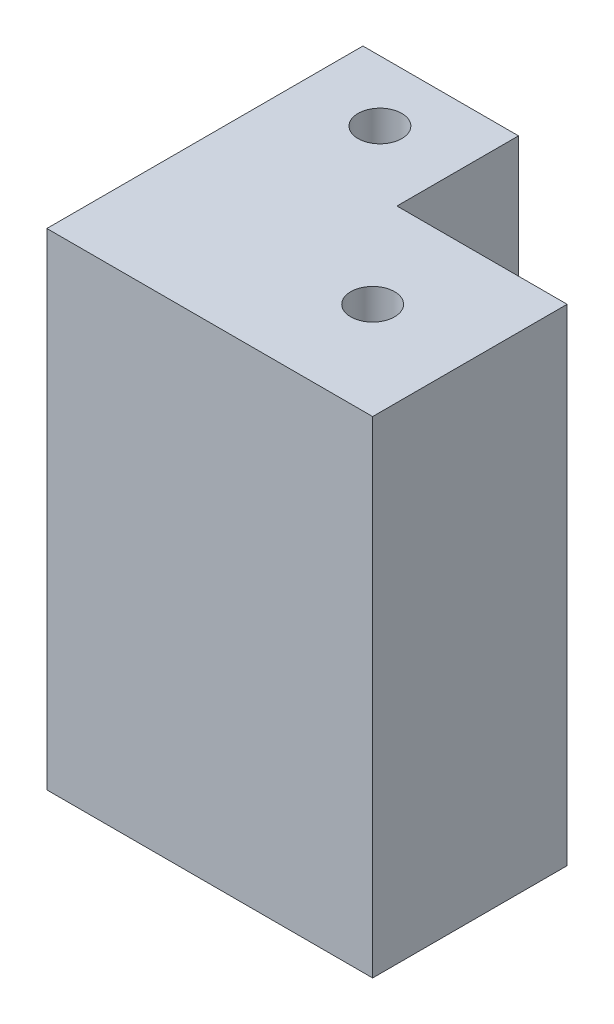
SolidWorks part; units mm, degrees
ref_plane "Front Plane" through (0, 0, 0) normal (0, 0, 1) x (1, 0, 0)
ref_plane "Top Plane" through (0, 0, 0) normal (0, 1, 0) x (1, 0, 0)
ref_plane "Right Plane" through (0, 0, 0) normal (1, 0, 0) x (0, 0, -1)
sketch "Sketch1" plane through (0, 0, 0) normal (0, 1, 0) x (1, 0, 0)
  line L0 (0, 0) -> (0, 25)
  line L1 (0, 25) -> (-32, 25)
  line L2 (-32, 25) -> (-32, -40)
  line L3 (-32, -40) -> (35, -40)
  line L4 (35, -40) -> (35, 0)
  line L5 (35, 0) -> (0, 0)
  line L6 (-32, 0) -> (0, 0) construction
  line L7 (0, -40) -> (0, 0) construction
  line L8 (0, 25) -> (-32, 0) construction
  line L9 (25, 25) -> (25, 0) construction
  line L10 (0, 25) -> (25, 25) construction
  line L11 (25, 0) -> (5, -40) construction
  line L12 (5, 5) -> (5, -40) construction
  line L13 (25, 25) -> (5, 25) construction
  line L14 (25, 25) -> (25, 5) construction
  line L15 (25, 5) -> (5, 5) construction
  line L16 (5, 25) -> (5, 5) construction
  circle A0 centre (-16, 12.5) radius 4.5
  circle A1 centre (15, -20) radius 4.5
  circle A2 centre (-16, 12.5) radius 11 construction
  circle A3 centre (-16, 12.5) radius 6 construction
  circle A4 centre (15, -20) radius 6.75 construction
  circle A5 centre (15, -20) radius 16 construction
  dimension "D4" = 9
  dimension "D5" = 22
  dimension "D6" = 12
  dimension "D7" = 13.5
  dimension "D8" = 32
  dimension "D1" = 25
  dimension "D2" = 25
  dimension "D3" = 40
  dimension "D9" = 32
  dimension "D10" = 20
  dimension "D11" = 20
extrude "Boss-Extrude1" add sketch "Sketch1" along normal blind 100
ref_plane "Plane1" through (0, 0, 0) normal (0, -1, 0) x (-1, 0, 0)
sketch "Sketch8" plane through (0, 0, 0) normal (0, -1, 0) x (-1, 0, 0)
  point P0 (-15, -20)
hole_wizard "CBORE for M5 Hex Head Bolt2" positions "Sketch8" profile "Sketch9" counterbore size "M5" standard "ANSI Metric"
sketch "Sketch9" plane through (15, 0, 20) normal (1, 0, 0) x (0, 0, -1)
  line L0 (0, 0) -> (0, 23.85)
  line L1 (0, 23.85) -> (6.75, 23.85)
  line L2 (6.75, 23.85) -> (6.75, 5)
  line L3 (6.75, 5) -> (16, 5)
  line L4 (16, 5) -> (16, 0)
  line L5 (16, 0) -> (0, 0)
  line L10 (0, 23.85) -> (-6.75, 23.85) construction
  line L11 (0, -6.35) -> (0, 107.95) construction
  dimension "Hole Dia." = 13.5
  dimension "Hole Depth" = 23.85
  dimension "C'Bore Dia." = 32
  dimension "C'Bore Depth" = 5
  dimension "Drill Angle" = 180
sketch "Sketch10" plane through (0, 0, 0) normal (0, -1, 0) x (-1, 0, 0)
  point P0 (16, 12.5)
hole_wizard "CBORE for M5 Hex Head Bolt3" positions "Sketch10" profile "Sketch11" counterbore size "M5" standard "ANSI Metric"
sketch "Sketch11" plane through (-16, 0, -12.5) normal (1, 0, 0) x (0, 0, -1)
  line L0 (0, 0) -> (0, 13.5)
  line L1 (0, 13.5) -> (5.1, 13.5)
  line L2 (5.1, 13.5) -> (5.1, 3.5)
  line L3 (5.1, 3.5) -> (11, 3.5)
  line L4 (11, 3.5) -> (11, 0)
  line L5 (11, 0) -> (0, 0)
  line L10 (0, 13.5) -> (-5.1, 13.5) construction
  line L11 (0, -6.35) -> (0, 107.95) construction
  dimension "Hole Dia." = 10.2
  dimension "Hole Depth" = 13.5
  dimension "C'Bore Dia." = 22
  dimension "C'Bore Depth" = 3.5
  dimension "Drill Angle" = 180
